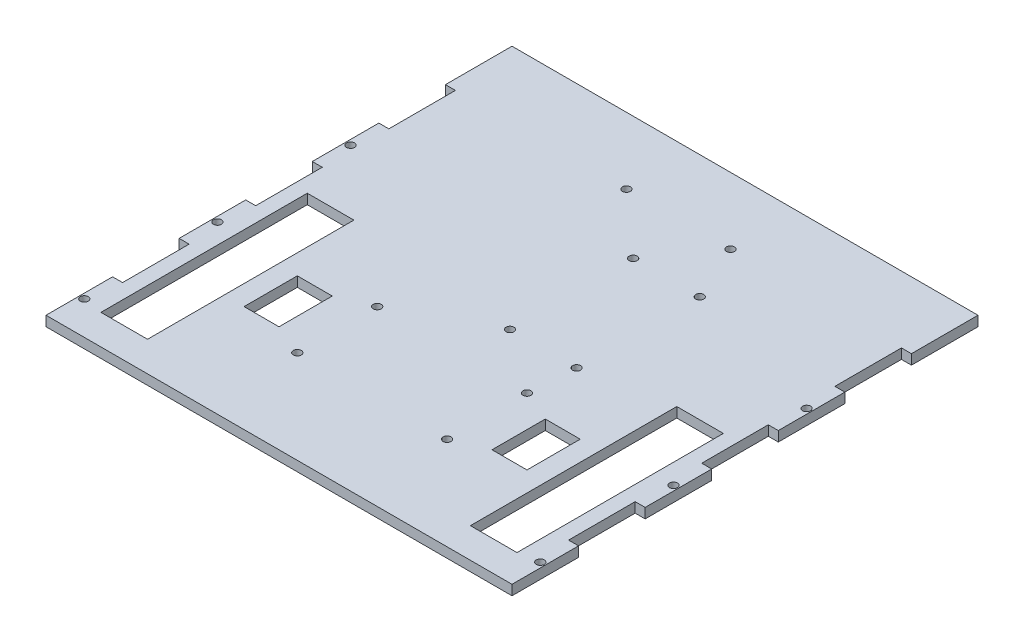
SolidWorks part; units mm, degrees
material "Acrylic (Medium-high impact)"
ref_plane "Front" through (0, 0, 0) normal (0, 0, 1) x (1, 0, 0)
ref_plane "Top" through (0, 0, 0) normal (0, 1, 0) x (1, 0, 0)
ref_plane "Right" through (0, 0, 0) normal (1, 0, 0) x (0, 0, -1)
sketch "Sketch1" plane through (0, 0, 0) normal (0, 1, 0) x (1, 0, 0)
  line L0 (-85.09, 0) -> (85.09, 0) construction
  line L5 (-88.9, -88.9) -> (88.9, -88.9)
  line L7 (-88.9, 88.9) -> (88.9, 88.9)
  line L9 (0, 88.9) -> (0, -88.9) construction
  line L10 (-28.575, -22.86) -> (-28.575, -53.34) construction
  line L11 (-40.64, -27.94) -> (-53.975, -27.94)
  line L12 (-40.64, -27.94) -> (-40.64, -48.26)
  line L13 (-40.64, -48.26) -> (-53.975, -48.26)
  line L14 (-53.975, -27.94) -> (-53.975, -48.26)
  line L15 (-88.9, -38.1) -> (88.9, -38.1) construction
  line L16 (61.595, 1.27) -> (61.595, -77.47)
  line L17 (-79.375, 1.27) -> (-61.595, 1.27)
  line L18 (-79.375, 1.27) -> (-79.375, -77.47)
  line L19 (-79.375, -77.47) -> (-61.595, -77.47)
  line L20 (-61.595, 1.27) -> (-61.595, -77.47)
  line L21 (79.375, -77.47) -> (61.595, -77.47)
  line L22 (79.375, 1.27) -> (79.375, -77.47)
  line L23 (79.375, 1.27) -> (61.595, 1.27)
  line L24 (53.975, -27.94) -> (53.975, -48.26)
  line L25 (40.64, -48.26) -> (53.975, -48.26)
  line L26 (40.64, -27.94) -> (40.64, -48.26)
  line L27 (40.64, -27.94) -> (53.975, -27.94)
  line L28 (88.9, 63.5) -> (85.09, 63.5)
  line L29 (85.09, 63.5) -> (85.09, 38.1)
  line L30 (85.09, 38.1) -> (88.9, 38.1)
  line L31 (88.9, 63.5) -> (88.9, 88.9)
  line L32 (88.9, 12.7) -> (88.9, 38.1)
  line L33 (88.9, 12.7) -> (85.09, 12.7)
  line L34 (85.09, 12.7) -> (85.09, -12.7)
  line L35 (85.09, -12.7) -> (88.9, -12.7)
  line L36 (88.9, -38.1) -> (88.9, -12.7)
  line L37 (88.9, -38.1) -> (85.09, -38.1)
  line L38 (85.09, -38.1) -> (85.09, -63.5)
  line L39 (85.09, -63.5) -> (88.9, -63.5)
  line L40 (88.9, -63.5) -> (88.9, -88.9)
  line L41 (-88.9, 63.5) -> (-88.9, 88.9)
  line L42 (-88.9, -63.5) -> (-88.9, -88.9)
  line L43 (-85.09, -63.5) -> (-88.9, -63.5)
  line L44 (-85.09, -38.1) -> (-85.09, -63.5)
  line L45 (-88.9, -38.1) -> (-85.09, -38.1)
  line L46 (-88.9, -38.1) -> (-88.9, -12.7)
  line L47 (-85.09, -12.7) -> (-88.9, -12.7)
  line L48 (-85.09, 12.7) -> (-85.09, -12.7)
  line L49 (-88.9, 12.7) -> (-85.09, 12.7)
  line L50 (-88.9, 12.7) -> (-88.9, 38.1)
  line L51 (-85.09, 38.1) -> (-88.9, 38.1)
  line L52 (-85.09, 63.5) -> (-85.09, 38.1)
  line L53 (-88.9, 63.5) -> (-85.09, 63.5)
  line L54 (88.9, -76.2) -> (-88.9, -76.2) construction
  line L55 (86.995, -63.5) -> (86.995, -88.9) construction
  line L56 (86.995, -76.2) -> (-86.995, -76.2) construction
  line L57 (86.995, -76.2) -> (86.995, -25.4) construction
  circle A0 centre (-28.575, -22.86) radius 1.524
  circle A1 centre (-28.575, -53.34) radius 1.524
  circle A2 centre (28.575, -53.34) radius 1.524
  circle A3 centre (28.575, -22.86) radius 1.524
  circle A4 centre (4.318, 41.91) radius 1.524
  circle A5 centre (4.318, -5.08) radius 1.524
  circle A6 centre (29.718, -5.08) radius 1.524
  circle A7 centre (29.718, 41.91) radius 1.524
  circle A11 centre (86.995, -76.2) radius 1.524
  circle A16 centre (-86.995, -76.2) radius 1.524
  circle A17 centre (-86.995, -25.4) radius 1.524
  circle A18 centre (-86.995, 25.4) radius 1.524
  circle A19 centre (86.995, -25.4) radius 1.524
  circle A20 centre (86.995, 25.4) radius 1.524
  circle A21 centre (-19.8501, 63.5) radius 1.524
  circle A22 centre (19.8501, 63.5) radius 1.524
  point P0 (0, 0)
  point P11 (0, 0)
  point P17 (-61.595, -38.1)
  point P18 (-28.575, -38.1)
  point P20 (-40.64, -38.1)
  point P73 (-85.09, 0)
  point P94 (-13.4033, 61.8279)
  dimension "D4" = 3.048
  dimension "D13" = 3.048
  dimension "D22" = 3.048
  dimension "D1" = 177.8
  dimension "D2" = 177.8
  dimension "D3" = 30.48
  dimension "D5" = 20.32
  dimension "D6" = 13.335
  dimension "D7" = 78.74
  dimension "D8" = 17.78
  dimension "D9" = 25.4
  dimension "D10" = 50.8
  dimension "D11" = 50.8
  dimension "D12" = 57.15
  dimension "D14" = 46.99
  dimension "D15" = 25.4
  dimension "D16" = 3
  dimension "D17" = 46.99
  dimension "D18" = 25.4
  dimension "D19" = 3.81
  dimension "D20" = 25.4
  dimension "D21" = 93.218
  dimension "D23" = 2
  dimension "D25" = 173.99
  dimension "D26" = 50.8
  dimension "D27" = 90
  dimension "D28" = 39.7002
  dimension "D29" = 25.4
  dimension "D24" = 3
extrude "Boss-Extrude1" add sketch "Sketch1" along normal blind 3.81
